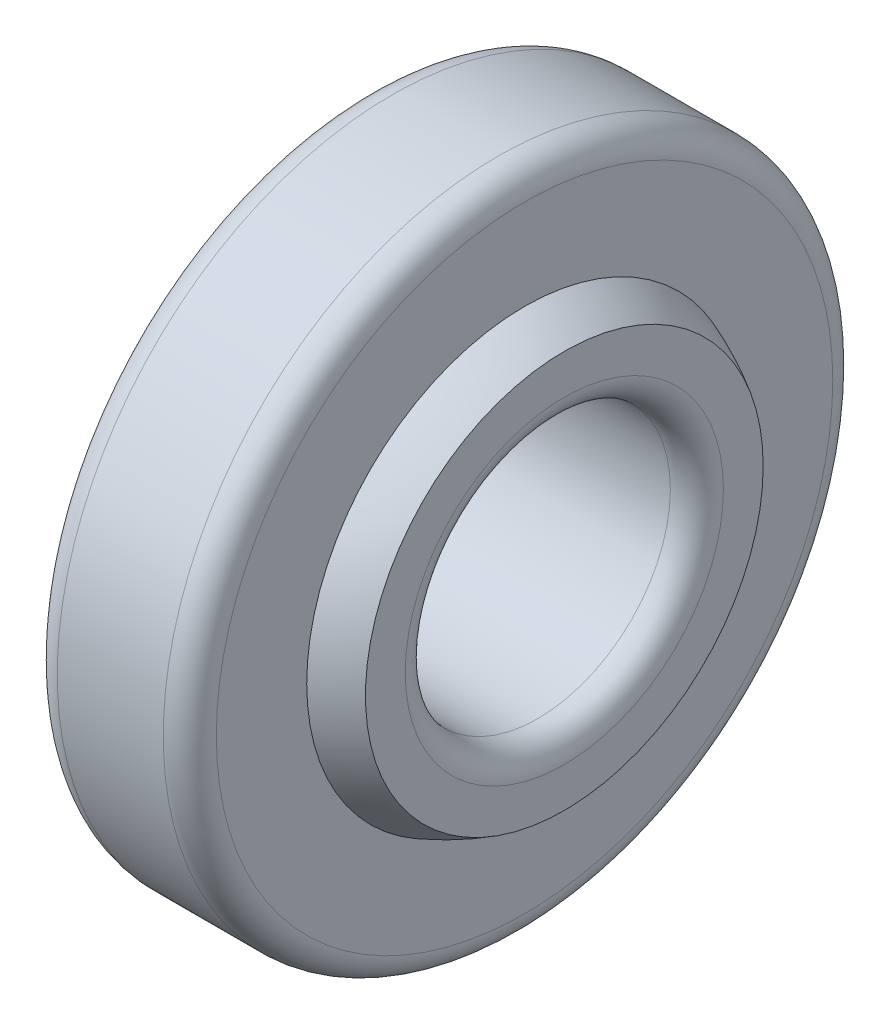
SolidWorks part; units mm, degrees
material "AISI 304"
ref_plane "前视基准面" through (0, 0, 0) normal (0, 0, 1) x (1, 0, 0)
ref_plane "上视基准面" through (0, 0, 0) normal (0, 1, 0) x (1, 0, 0)
ref_plane "右视基准面" through (0, 0, 0) normal (1, 0, 0) x (0, 0, -1)
sketch "Sketch1" plane through (0, 0, 0) normal (0, 1, 0) x (1, 0, 0)
  line L0 (0, 0) -> (15.5109, 0) construction
  line L1 (0, 0) -> (0, 2.525) construction
  line L2 (-0.6, 2.525) -> (0.6, 2.525)
  line L3 (-0.6, 2.525) -> (-0.6, 1)
  line L4 (-0.6, -2.525) -> (0.6, -2.525)
  line L5 (0.6, 2.525) -> (0.6, 1)
  line L7 (-0.9, 1.5) -> (-0.9, 1)
  line L9 (0.9, 1.5) -> (0.9, 1)
  line L10 (0.9, -1) -> (0.9, -1.5)
  line L11 (-0.9, 1) -> (0.9, 1)
  line L13 (-0.9, -1) -> (0.9, -1)
  line L15 (0.6, -1) -> (0.6, -2.525)
  line L16 (-0.6, -1) -> (-0.6, -2.525)
  line L17 (-0.9, -1) -> (-0.9, -1.5)
  arc A0 (0.9, 1.5) -> (-0.9, 1.5) centre (0, 0) ccw
  arc A1 (-0.9, -1.5) -> (0.9, -1.5) centre (0, 0) ccw
  dimension "C" = 1.2
  dimension "B" = 1.8
  dimension "d" = 2
  dimension "d2" = 3
  dimension "d3" = 5.05
revolve "Revolve1" add sketch "Sketch1" angle 360 about L0 region at (0, 0, -2.1191)
fillet "Fillet1" radius 0.2 4 edges at (-0.9, 0, 1) (0.9, 0, 1) (-0.6, 0, 2.525) (0.6, 0, 2.525)
